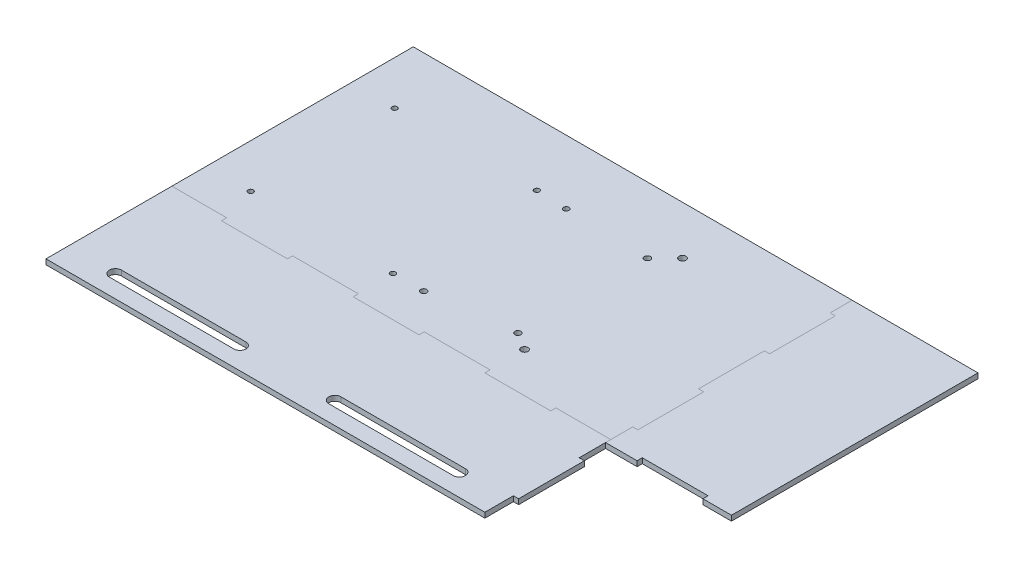
SolidWorks part; units mm, degrees
ref_plane "Front Plane" through (0, 0, 0) normal (0, 0, 1) x (1, 0, 0)
ref_plane "Top Plane" through (0, 0, 0) normal (0, 1, 0) x (1, 0, 0)
ref_plane "Right Plane" through (0, 0, 0) normal (1, 0, 0) x (0, 0, -1)
sketch "Sketch1" plane through (0, 0, 0) normal (0, 1, 0) x (1, 0, 0)
  line L0 (0, 0) -> (31.75, 0)
  line L1 (0, 0) -> (0, 139.7)
  line L2 (254, 0) -> (254, 12.7)
  line L3 (0, 139.7) -> (254, 139.7)
  line L4 (127, 0) -> (127, -33.6267) construction
  line L5 (107.95, 0) -> (107.95, -3)
  line L6 (107.95, -3) -> (146.05, -3)
  line L7 (146.05, -3) -> (146.05, 0)
  line L8 (222.25, -3) -> (222.25, 0)
  line L9 (184.15, -3) -> (222.25, -3)
  line L10 (184.15, 0) -> (184.15, -3)
  line L11 (69.85, 0) -> (69.85, -3)
  line L12 (69.85, -3) -> (31.75, -3)
  line L13 (31.75, -3) -> (31.75, 0)
  line L14 (69.85, 0) -> (107.95, 0)
  line L15 (146.05, 0) -> (184.15, 0)
  line L16 (222.25, 0) -> (254, 0)
  line L17 (254, 69.85) -> (265.2781, 69.85) construction
  line L18 (254, 127) -> (257, 127)
  line L19 (257, 127) -> (257, 88.9)
  line L20 (257, 88.9) -> (254, 88.9)
  line L21 (254, 12.7) -> (257, 12.7)
  line L22 (257, 50.8) -> (254, 50.8)
  line L23 (257, 12.7) -> (257, 50.8)
  line L24 (254, 127) -> (254, 139.7)
  line L25 (254, 50.8) -> (254, 88.9)
  dimension "D1" = 254
  dimension "D2" = 139.7
  dimension "D3" = 19.05
  dimension "D4" = 38.1
  dimension "D5" = 3
  dimension "D7" = 38.1
  dimension "D8" = 3
  dimension "D9" = 19.05
  dimension "D6" = 2
extrude "Boss-Extrude1" add sketch "Sketch1" along normal blind 3
sketch "Sketch2" plane through (0, 0, 0) normal (0, 1, 0) x (1, 0, 0)
  line L0 (0, 0) -> (31.75, 0)
  line L1 (0, 0) -> (0, -72.85)
  line L2 (254, 0) -> (254, -18.24)
  line L3 (0, -72.85) -> (254, -72.85)
  line L4 (0, 139.7) -> (0, 0) construction
  line L5 (107.95, 0) -> (107.95, -3)
  line L6 (107.95, -3) -> (146.05, -3)
  line L7 (146.05, -3) -> (146.05, 0)
  line L8 (127, 0) -> (127, -39.0108) construction
  line L9 (222.25, -3) -> (222.25, 0)
  line L10 (184.15, -3) -> (222.25, -3)
  line L11 (184.15, 0) -> (184.15, -3)
  line L12 (69.85, 0) -> (69.85, -3)
  line L13 (69.85, -3) -> (31.75, -3)
  line L14 (31.75, -3) -> (31.75, 0)
  line L15 (69.85, 0) -> (107.95, 0)
  line L16 (146.05, 0) -> (184.15, 0)
  line L17 (222.25, 0) -> (254, 0)
  line L18 (222.25, 0) -> (254, 0) construction
  line L19 (254, -36.425) -> (264.3748, -36.425) construction
  line L20 (254, -18.24) -> (257, -18.24)
  line L21 (257, -18.24) -> (257, -56.34)
  line L22 (257, -56.34) -> (254, -56.34)
  line L23 (254, -56.34) -> (254, -72.85)
  dimension "D1" = 254
  dimension "D2" = 72.85
  dimension "D3" = 19.05
  dimension "D4" = 38.1
  dimension "D5" = 3
  dimension "D7" = 0
  dimension "D8" = 38.1
  dimension "D9" = 3
  dimension "D10" = 16.51
  dimension "D6" = 2
extrude "Boss-Extrude2" add sketch "Sketch2" along normal blind 3 separate body
sketch "Sketch3" plane through (0, 0, 0) normal (0, 1, 0) x (1, 0, 0)
  line L0 (254, 139.7) -> (0, 139.7) construction
  line L1 (254, -3) -> (254, 12.7)
  line L2 (326.85, -3) -> (326.85, 139.7)
  line L3 (254, 139.7) -> (326.85, 139.7)
  line L4 (254, -3) -> (272.24, -3)
  line L5 (254, 127) -> (257, 127)
  line L6 (257, 127) -> (257, 88.9)
  line L7 (257, 88.9) -> (254, 88.9)
  line L8 (257, 50.8) -> (254, 50.8)
  line L9 (257, 12.7) -> (257, 50.8)
  line L10 (254, 12.7) -> (257, 12.7)
  line L11 (254, 127) -> (254, 139.7)
  line L12 (254, 50.8) -> (254, 88.9)
  line L13 (254, 0) -> (254, 12.7) construction
  line L14 (326.85, 68.35) -> (313.8041, 68.35) construction
  line L16 (254, 88.9) -> (257, 88.9) construction
  line L17 (257, 50.8) -> (254, 50.8) construction
  line L18 (272.24, -3) -> (272.24, 0)
  line L19 (272.24, 0) -> (310.34, 0)
  line L20 (310.34, 0) -> (310.34, -3)
  line L21 (310.34, -3) -> (326.85, -3)
  dimension "D1" = 142.7
  dimension "D2" = 72.85
  dimension "D3" = 3
  dimension "D4" = 38.1
  dimension "D5" = 0
  dimension "D6" = 0
  dimension "D7" = 0
  dimension "D8" = 0
  dimension "D9" = 38.1
  dimension "D10" = 16.51
  dimension "D11" = 3
  dimension "D12" = 38.1
extrude "Boss-Extrude3" add sketch "Sketch3" along normal blind 3 separate body
sketch "Sketch4" plane through (0, 3, 0) normal (0, 1, 0) x (1, 0, 0)
  line L0 (27.4554, -60.15) -> (99.5446, -60.15) construction
  line L1 (27.4554, -56.65) -> (99.5446, -56.65)
  line L2 (27.4554, -63.65) -> (99.5446, -63.65)
  line L3 (0, -72.85) -> (254, -72.85) construction
  line L4 (127, -72.85) -> (127, -72.1755) construction
  line L5 (226.5446, -60.15) -> (154.4554, -60.15) construction
  line L6 (226.5446, -56.65) -> (154.4554, -56.65)
  line L7 (226.5446, -63.65) -> (154.4554, -63.65)
  arc A0 (27.4554, -56.65) -> (27.4554, -63.65) centre (27.4554, -60.15) ccw
  arc A1 (99.5446, -63.65) -> (99.5446, -56.65) centre (99.5446, -60.15) ccw
  arc A2 (226.5446, -56.65) -> (226.5446, -63.65) centre (226.5446, -60.15) cw
  arc A3 (154.4554, -63.65) -> (154.4554, -56.65) centre (154.4554, -60.15) cw
  point P2 (63.5, -60.15)
  point P9 (127, -72.85)
  point P14 (190.5, -60.15)
  dimension "D2" = 3.5
  dimension "D1" = 12.7
  dimension "D3" = 63.5
extrude "Cut-Extrude1" cut sketch "Sketch4" against normal blind 3
sketch "Sketch5" plane through (0, 3, 0) normal (0, 1, 0) x (1, 0, 0)
  line L0 (0, 139.7) -> (0, 0) construction
  circle A0 centre (25.4, 20.2078) radius 1.5
  circle A1 centre (25.4, 103.5198) radius 1.5
  circle A2 centre (107.7, 20.2078) radius 1.5
  circle A3 centre (107.7, 103.5198) radius 1.5
  circle A4 centre (173.74, 101.4878) radius 1.75
  circle A5 centre (173.74, 26.5578) radius 1.75
  circle A6 centre (125.48, 20.2078) radius 1.75
  circle A7 centre (125.48, 102.7578) radius 1.5888
  circle A8 centre (183.9, 111.6478) radius 2
  circle A9 centre (183.9, 20.2078) radius 2
  dimension "D2" = 3
  dimension "D3" = 3
  dimension "D5" = 3
  dimension "D6" = 3
  dimension "D10" = 3.5
  dimension "D11" = 3.5
  dimension "D13" = 3.5
  dimension "D19" = 4
  dimension "D20" = 4
  dimension "D1" = 83.312
  dimension "D4" = 82.3
  dimension "D7" = 82.3
  dimension "D8" = 83.312
  dimension "D9" = 74.93
  dimension "D12" = 82.55
  dimension "D14" = 48.26
  dimension "D15" = 1.27
  dimension "D16" = 25.4
  dimension "D17" = 17.78
  dimension "D18" = 0
  dimension "D21" = 91.44
  dimension "D22" = 0
  dimension "D23" = 10.16
extrude "Cut-Extrude2" cut sketch "Sketch5" against normal blind 3
